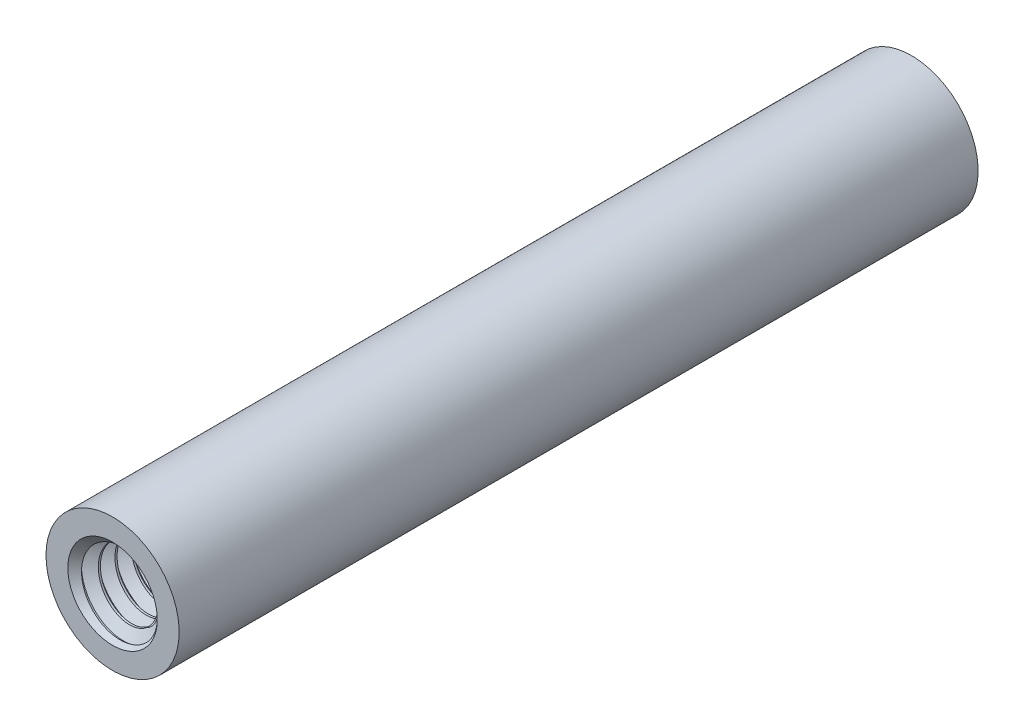
SolidWorks part; units mm, degrees
ref_plane "Front Plane" through (0, 0, 0) normal (0, 0, 1) x (1, 0, 0)
ref_plane "Top Plane" through (0, 0, 0) normal (0, 1, 0) x (1, 0, 0)
ref_plane "Right Plane" through (0, 0, 0) normal (1, 0, 0) x (0, 0, -1)
sketch "Sketch3" plane through (0, 0, 0) normal (1, 0, 0) x (0, 0, -1)
  line L0 (-19.05, 0) -> (19.05, 0) construction
  line L1 (0, 3.175) -> (0, -3.175) construction
  line L2 (-19.05, 2.0828) -> (-19.05, -2.0828) construction
  point P2 (7.9375, 0)
  point P3 (-7.9375, 0)
  dimension "Length" = 38.1
  dimension "Min Thread Length" = 11.1125
  dimension "D1" = 11.1125
  dimension "Thread Dia" = 4.1656
  dimension "OD" = 6.35
sketch "Sketch1" plane through (0, 0, 0) normal (0, 0, 1) x (1, 0, 0)
  circle A1 centre (0, 0) radius 2.0828
  circle A2 centre (0, 0) radius 3.175
extrude "Extrude1" add sketch "Sketch1" along normal up to vertex (19.05 mm away) and the other way up to vertex (19.05 mm away) up to point (0, 0, 19.05) other way up to point (0, 0, -19.05)
sketch "Sketch11" plane through (0, 0, -19.05) normal (0, 0, -1) x (-1, 0, 0)
  circle A0 centre (0, 0) radius 2.0828 construction
  circle A1 centre (0, 0) radius 2.0828
curve "Helix/Spiral1" pitch 0.7937 height 38.8938 turns 49 parameters "Pitch"=0.7937
sketch "Sketch12" plane through (0, 0, 0) normal (1, 0, 0) x (0, 0, -1)
  line L0 (19.7445, 2.0828) -> (19.05, 2.0828)
  line L1 (19.7445, 2.0828) -> (19.4469, 1.5672)
  line L2 (19.4469, 1.5672) -> (19.3477, 1.5672)
  line L3 (19.3477, 1.5672) -> (19.05, 2.0828)
  line L4 (19.3973, 1.5672) -> (19.3973, 2.0828) construction
  line L5 (19.5957, 1.825) -> (19.1988, 1.825) construction
  dimension "D1" = 0.0992
  dimension "D2" = 0.3969
  dimension "D3" = 60
sweep "Sweep1" add profiles "Sketch12" path "Helix/Spiral1"
sketch "Sketch6" plane through (0, 0, -19.05) normal (0, 0, -1) x (-1, 0, 0)
  circle A1 centre (0, 0) radius 3.175
  circle A2 centre (0, 0) radius 3.175
  dimension "D1" = 0
extrude "Extrude2" cut sketch "Sketch6" along normal through all
sketch "Sketch7" plane through (0, 0, -19.05) normal (0, 0, -1) x (-1, 0, 0)
  circle A2 centre (0, 0) radius 2.1336
  circle A3 centre (0, 0) radius 2.1336
  dimension "D1" = 0.0508
extrude "Extrude3" cut sketch "Sketch7" against normal through all draft 43
mirror "Mirror1" about plane through (0, 0, 0) normal (0, 0, 1) of "Extrude2", "Extrude3"
sketch "Sketch9" plane through (0, 0, 0) normal (1, 0, 0) x (0, 0, -1)
  line L1 (-7.9375, 2.1336) -> (7.9375, 2.1336)
  line L2 (-7.9375, 2.1336) -> (-7.9375, 0)
  line L3 (-7.9375, 0) -> (7.9375, 0)
  line L4 (7.9375, 2.1336) -> (7.9375, 0)
  line L7 (-19.05, 0) -> (19.05, 0) construction
revolve "Revolve" add sketch "Sketch9" angle 360 about L0
sketch "Sketch10" plane through (0, 0, 0) normal (1, 0, 0) x (0, 0, -1)
  line L0 (19.05, 2.0828) -> (7.9375, 2.0828)
  line L1 (-19.05, 2.0828) -> (-7.9375, 2.0828)
  line L2 (7.9375, 2.0828) -> (7.9375, -2.0828)
  line L3 (-19.05, -2.1336) -> (-7.9375, -2.1336)
  line L4 (-7.9375, 2.0828) -> (-7.9375, -2.1336)
  line L5 (7.9375, -2.0828) -> (19.05, -2.0828)
equation "\"D1@Sketch3\" = \"Min Thread Length@Sketch3\""
equation "\"D3@Helix/Spiral1\" = \"Length@Sketch3\"+\"Pitch@Helix/Spiral1\""
equation "\"D1@Sketch12\" = \"Pitch@Helix/Spiral1\"*.125"
equation "\"D2@Sketch12\" = \"Pitch@Helix/Spiral1\"*.5"
